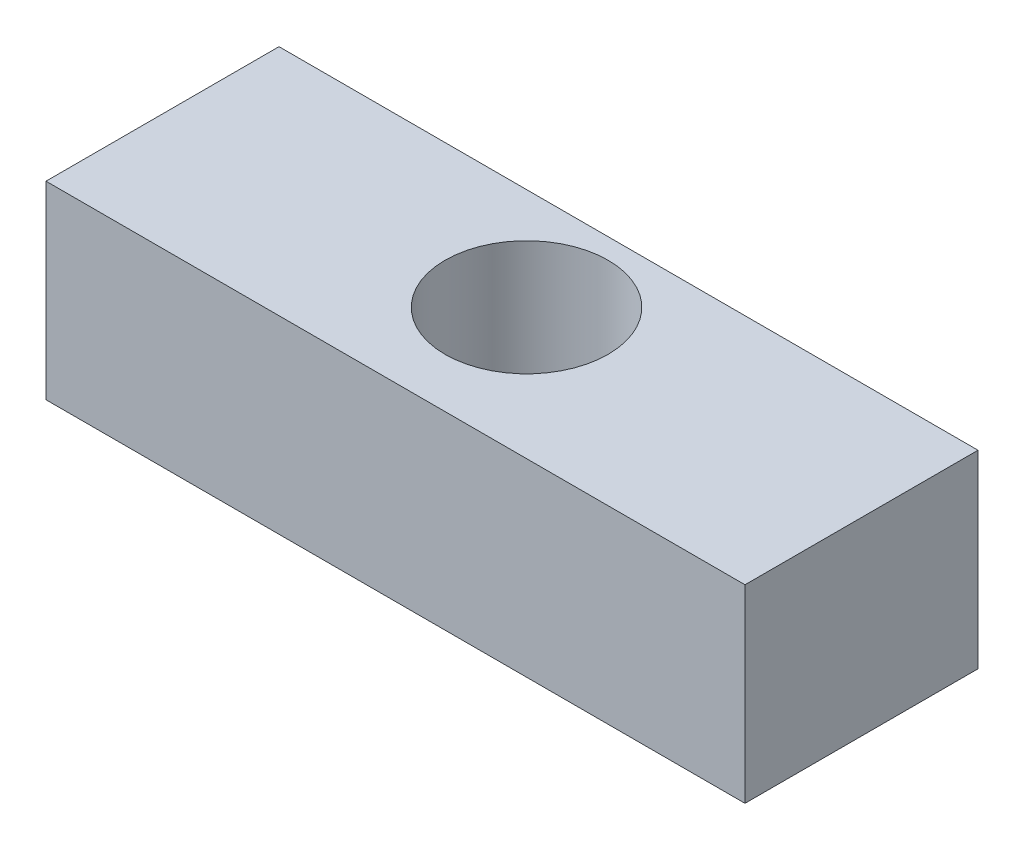
SolidWorks part; units mm, degrees
material "Polyethylene Cross-Linked"
ref_plane "Front Plane" through (0, 0, 0) normal (0, 0, 1) x (1, 0, 0)
ref_plane "Top Plane" through (0, 0, 0) normal (0, 1, 0) x (1, 0, 0)
ref_plane "Right Plane" through (0, 0, 0) normal (1, 0, 0) x (0, 0, -1)
sketch "Sketch1" plane through (0, 0, 0) normal (0, 1, 0) x (1, 0, 0)
  line L1 (0, 0) -> (38.1, 0)
  line L2 (0, 0) -> (0, 12.7)
  line L3 (0, 12.7) -> (38.1, 12.7)
  line L4 (38.1, 0) -> (38.1, 12.7)
  circle A0 centre (19.05, 7.1437) radius 4.445
  point P5 (19.05, 6.9002)
extrude "Boss-Extrude1" add sketch "Sketch1" along normal blind 10.3187
